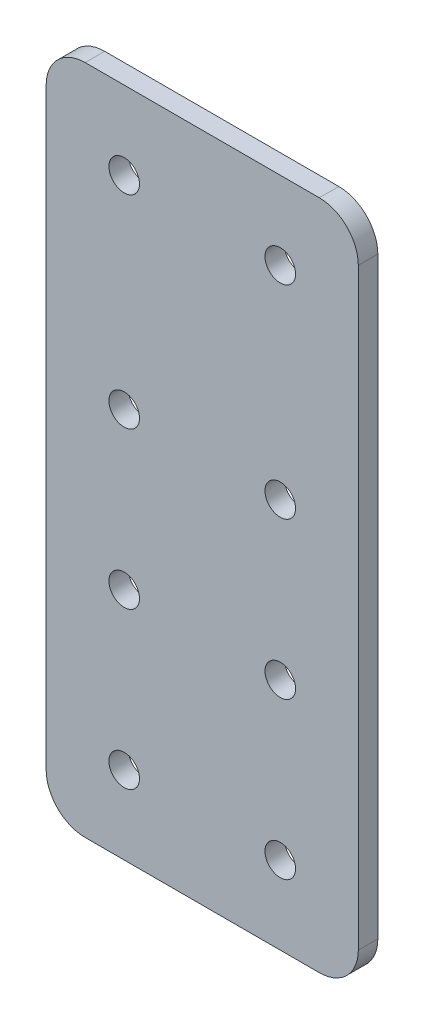
SolidWorks part; units mm, degrees
material "6061-T6 (SS)"
ref_plane "Front Plane" through (0, 0, 0) normal (0, 0, 1) x (1, 0, 0)
ref_plane "Top Plane" through (0, 0, 0) normal (0, 1, 0) x (1, 0, 0)
ref_plane "Right Plane" through (0, 0, 0) normal (1, 0, 0) x (0, 0, -1)
sketch "Sketch2" plane through (0, 0, 0) normal (0, 0, 1) x (1, 0, 0)
  line L1 (0, 0) -> (50.8, 0)
  line L2 (0, 0) -> (0, 109.22)
  line L3 (0, 109.22) -> (50.8, 109.22)
  line L4 (50.8, 0) -> (50.8, 109.22)
  dimension "D1" = 50.8
  dimension "D2" = 109.22
extrude "Boss-Extrude1" add sketch "Sketch2" against normal blind 3.175
sketch "Sketch3" plane through (0, 0, 0) normal (0, 0, 1) x (1, 0, 0)
  line L0 (50.8, 109.22) -> (0, 109.22) construction
  line L1 (0, 109.22) -> (0, 0) construction
  circle A0 centre (12.7, 96.52) radius 2.4892
  circle A17 centre (38.1, 96.52) radius 2.4892
  circle A24 centre (12.7, 63.5) radius 2.4892
  circle A25 centre (12.7, 38.1) radius 2.4892
  circle A26 centre (12.7, 12.7) radius 2.4892
  circle A27 centre (12.7, -12.7) radius 2.4892
  circle A28 centre (12.7, -38.1) radius 2.4892
  circle A33 centre (38.1, 38.1) radius 2.4892
  circle A34 centre (38.1, 12.7) radius 2.4892
  circle A35 centre (38.1, -12.7) radius 2.4892
  circle A36 centre (38.1, -38.1) radius 2.4892
  circle A41 centre (38.1, 63.5) radius 2.4892
  dimension "D1" = 4.9784
  dimension "D6" = 4.9784
  dimension "D2" = 12.7
  dimension "D3" = 12.7
  dimension "D7" = 12.7
  dimension "D8" = 33.02
  dimension "D4" = 1
  dimension "D5" = 2
  dimension "D9" = 5
  dimension "D10" = 2
extrude "Cut-Extrude1" cut sketch "Sketch3" against normal through all
fillet "Fillet1" radius 6.35 4 edges at (0, 0, -1.5875) (50.8, 0, -1.5875) (50.8, 109.22, -1.5875) (0, 109.22, -1.5875)
